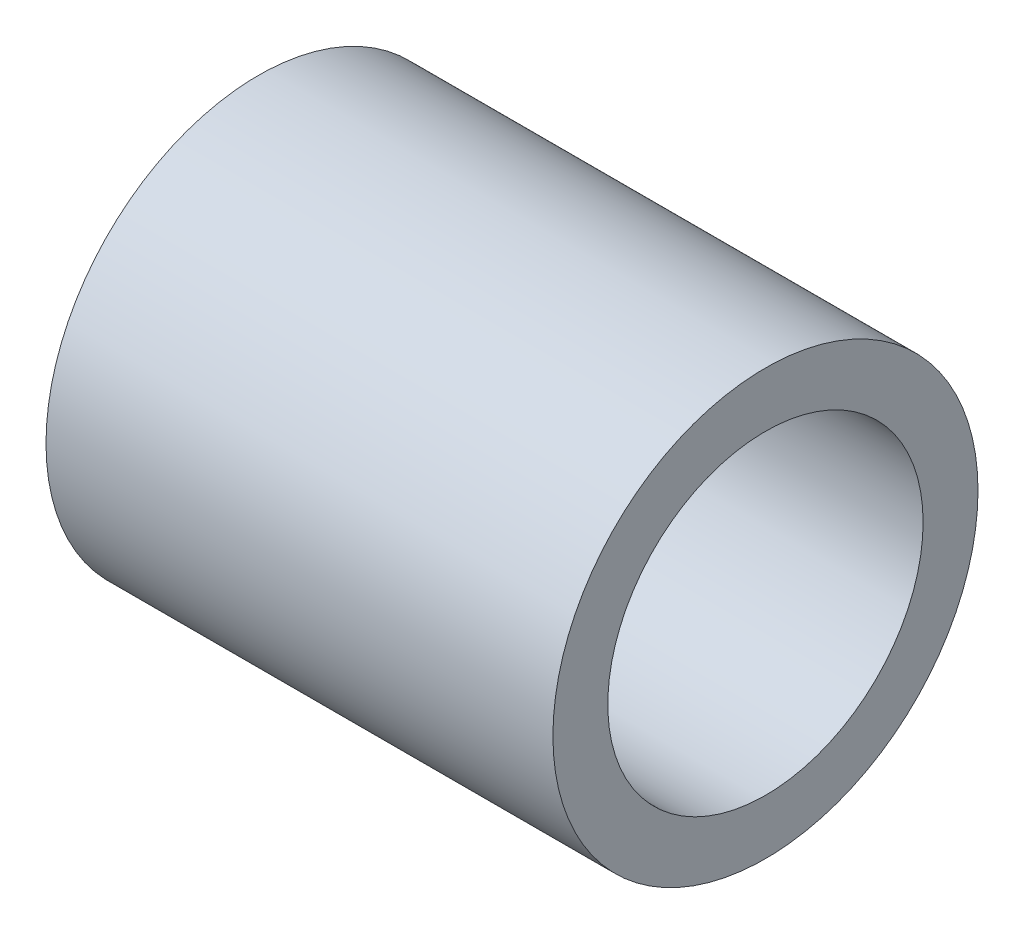
SolidWorks part; units mm, degrees
material "PVC Rígido"
ref_plane "Alzado" through (0, 0, 0) normal (0, 0, 1) x (1, 0, 0)
ref_plane "Planta" through (0, 0, 0) normal (0, 1, 0) x (1, 0, 0)
ref_plane "Vista lateral" through (0, 0, 0) normal (1, 0, 0) x (0, 0, -1)
sketch "Croquis1" plane through (0, 0, 0) normal (1, 0, 0) x (0, 0, -1)
  circle A0 centre (0, 0) radius 10.65
  circle A1 centre (0, 0) radius 7.9
  dimension "D1" = 21.3
  dimension "D2" = 15.8
extrude "Saliente-Extruir1" add sketch "Croquis1" along normal blind 25.4
